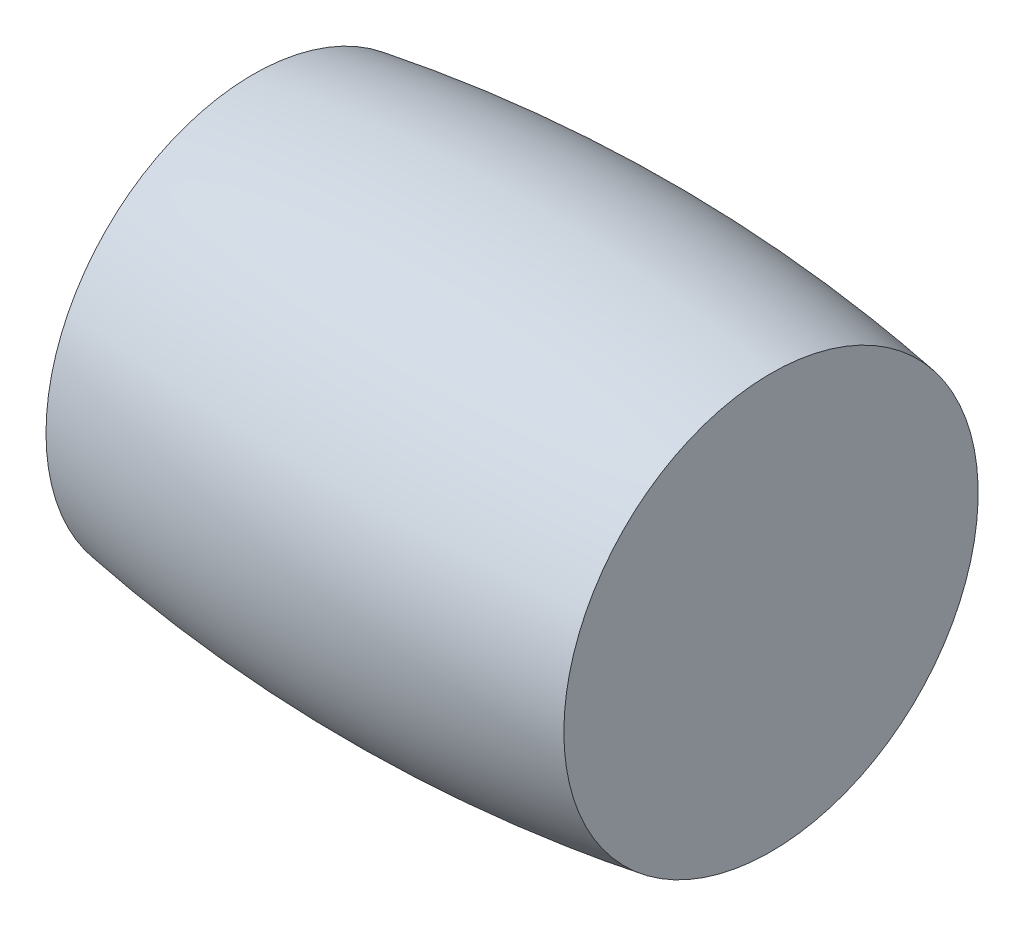
SolidWorks part; units mm, degrees
ref_plane "Front Plane" through (0, 0, 0) normal (0, 0, 1) x (1, 0, 0)
ref_plane "Top Plane" through (0, 0, 0) normal (0, 1, 0) x (1, 0, 0)
ref_plane "Right Plane" through (0, 0, 0) normal (1, 0, 0) x (0, 0, -1)
sketch "Sketch1" plane through (0, 0, 0) normal (0, 0, 1) x (1, 0, 0)
  line L0 (-7.5, 0) -> (7.5, 0) construction
  line L1 (0, 0) -> (0, 6.6) construction
  line L2 (-7.5, 0) -> (-7.5, 6)
  line L3 (7.5, 0) -> (7.5, 6)
  line L4 (-7.5, 0) -> (7.5, 0)
  arc A1 (7.5, 6) -> (-7.5, 6) centre (0, -40.575) ccw
  dimension "D1" = 15
  dimension "D2" = 6.6
  dimension "D3" = 6
revolve "Revolve1" add sketch "Sketch1" angle 360 about L4
ref_axis "Axis1" through (-9.0049, 0, 0) along (1, 0, 0)
